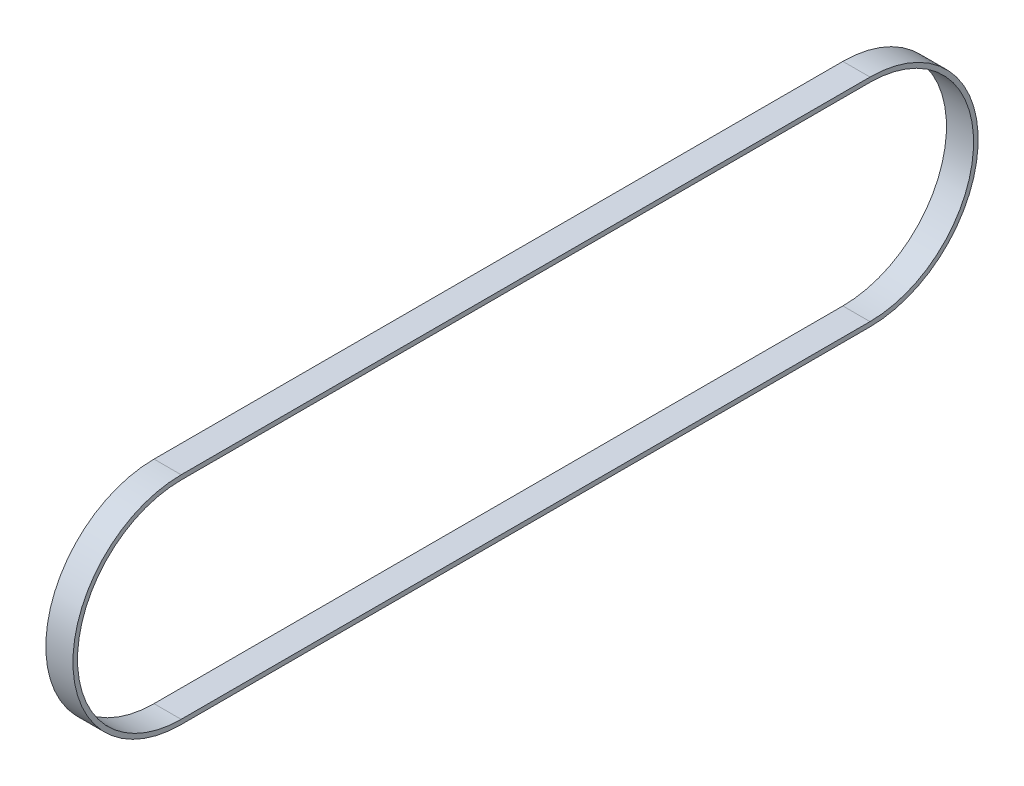
SolidWorks part; units mm, degrees
ref_plane "Front Plane" through (0, 0, 0) normal (0, 0, 1) x (1, 0, 0)
ref_plane "Top Plane" through (0, 0, 0) normal (0, 1, 0) x (1, 0, 0)
ref_plane "Right Plane" through (0, 0, 0) normal (1, 0, 0) x (0, 0, -1)
sketch "Sketch1" plane through (0, 0, 0) normal (1, 0, 0) x (0, 0, -1)
  line L0 (0, 0) -> (381, 0) construction
  line L1 (0, 57.3024) -> (381, 57.3024)
  line L2 (0, -57.3024) -> (381, -57.3024)
  line L3 (0, 0) -> (381, 0) construction
  line L4 (0, 59.8424) -> (381, 59.8424)
  line L5 (0, -59.8424) -> (381, -59.8424)
  arc A0 (0, 57.3024) -> (0, -57.3024) centre (0, 0) ccw
  arc A1 (381, -57.3024) -> (381, 57.3024) centre (381, 0) ccw
  arc A2 (0, 59.8424) -> (0, -59.8424) centre (0, 0) ccw
  arc A3 (381, -59.8424) -> (381, 59.8424) centre (381, 0) ccw
  point P3 (190.5, 0)
  point P8 (190.5, 0)
  dimension "D2" = 57.3024
  dimension "D3" = 59.8424
  dimension "D1" = 381
extrude "Boss-Extrude1" add sketch "Sketch1" along normal blind 15
